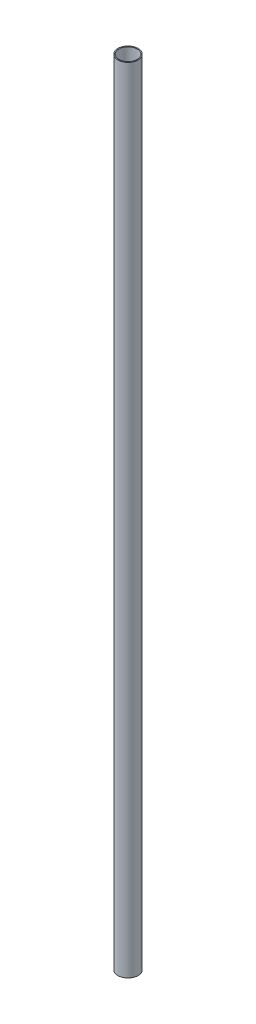
SolidWorks part; units mm, degrees
material "Zoltek Panex 33"
ref_plane "Front Plane" through (0, 0, 0) normal (0, 0, 1) x (1, 0, 0)
ref_plane "Top Plane" through (0, 0, 0) normal (0, 1, 0) x (1, 0, 0)
ref_plane "Right Plane" through (0, 0, 0) normal (1, 0, 0) x (0, 0, -1)
sketch "Sketch1" plane through (0, 0, 0) normal (0, 1, 0) x (1, 0, 0)
  circle A0 centre (0, 0) radius 12.7
  circle A1 centre (0, 0) radius 11.5
  dimension "D1" = 25.4
  dimension "D2" = 23
extrude "Boss-Extrude1" add sketch "Sketch1" along normal blind 1000
